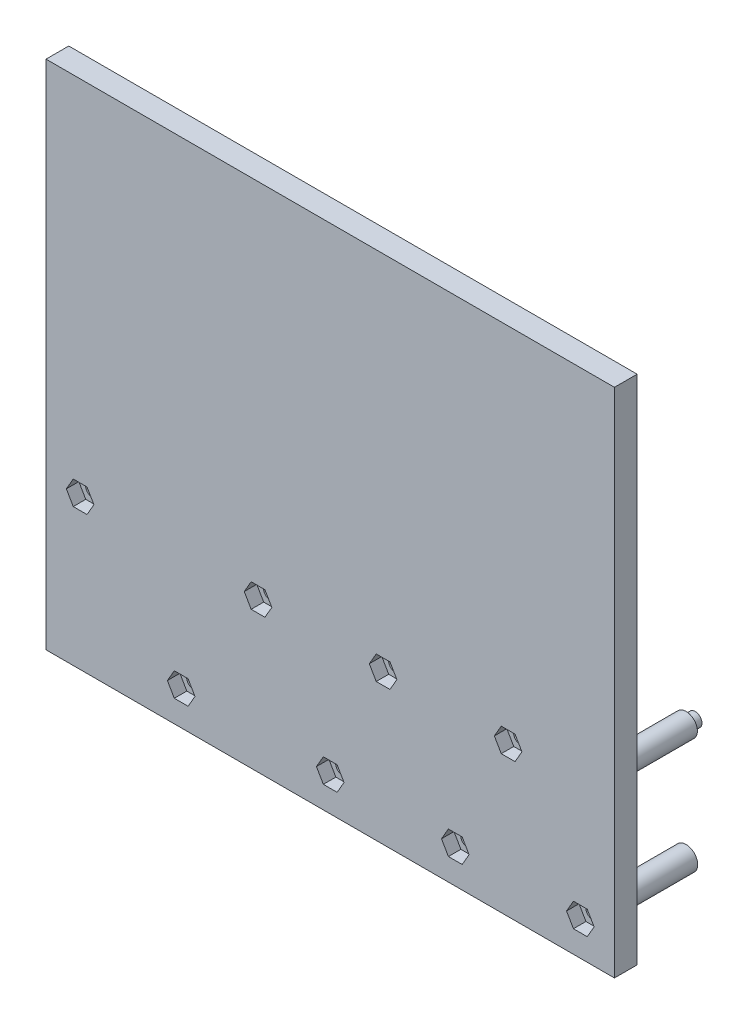
SolidWorks part; units mm, degrees
ref_plane "Front Plane" through (0, 0, 0) normal (0, 0, 1) x (1, 0, 0)
ref_plane "Top Plane" through (0, 0, 0) normal (0, 1, 0) x (1, 0, 0)
ref_plane "Right Plane" through (0, 0, 0) normal (1, 0, 0) x (0, 0, -1)
sketch "Sketch1" plane through (0, 0, 0) normal (0, 0, 1) x (1, 0, 0)
  line L1 (50, -45) -> (-50, -45)
  line L2 (50, -45) -> (50, 45)
  line L3 (50, 45) -> (-50, 45)
  line L4 (-50, -45) -> (-50, 45)
  line L5 (50, -45) -> (-50, 45) construction
  line L6 (50, 45) -> (-50, -45) construction
  point P0 (0, 0)
  dimension "D1" = 100
  dimension "D2" = 90
extrude "Boss-Extrude1" add sketch "Sketch1" along normal mid plane 4
sketch "Sketch2" plane through (0, 0, 2) normal (0, 0, 1) x (1, 0, 0)
  line L0 (50, -45) -> (50, 45) construction
  line L1 (-50, -45) -> (50, -45) construction
  circle A0 centre (44, -39) radius 1.25
  circle A1 centre (44, -18.68) radius 1.2
  circle A2 centre (31.3, -18.68) radius 1.25
  circle A3 centre (31.3, -39) radius 1.2
  circle A4 centre (31.3, -18.68) radius 2.05
  circle A5 centre (44, -18.68) radius 2
  circle A6 centre (31.3, -39) radius 2
  circle A7 centre (44, -39) radius 2.05
  dimension "D1" = 2.5
  dimension "D2" = 2.4
  dimension "D7" = 4
  dimension "D8" = 4.1
  dimension "D3" = 12.7
  dimension "D4" = 20.32
  dimension "D5" = 6
  dimension "D6" = 6
extrude "Boss-Extrude3" add sketch "Sketch2" against normal blind 18.6 contours A6 | A7 | A5 | A4
extrude "Cut-Extrude1" cut sketch "Sketch2<5>" against normal through all contours A2 | A0
sketch "Sketch2<5>" plane through (0, 0, 2) normal (0, 0, 1) x (1, 0, 0) same geometry as "Sketch2"
extrude "Boss-Extrude4" add sketch "Sketch2<6>" against normal blind 20.2 contours A3 | A1
sketch "Sketch2<6>" plane through (0, 0, 2) normal (0, 0, 1) x (1, 0, 0) same geometry as "Sketch2"
sketch "Sketch3" plane through (0, 0, 2) normal (0, 0, 1) x (1, 0, 0)
  line L0 (-50, -45) -> (50, -45) construction
  line L1 (30.0876, -16.58) -> (28.8751, -18.68)
  line L2 (28.8751, -18.68) -> (30.0876, -20.78)
  line L3 (30.0876, -20.78) -> (32.5124, -20.78)
  line L4 (32.5124, -20.78) -> (33.7249, -18.68)
  line L5 (33.7249, -18.68) -> (32.5124, -16.58)
  line L6 (32.5124, -16.58) -> (30.0876, -16.58)
  line L7 (42.7876, -36.9) -> (41.5751, -39)
  line L8 (41.5751, -39) -> (42.7876, -41.1)
  line L9 (42.7876, -41.1) -> (45.2124, -41.1)
  line L10 (45.2124, -41.1) -> (46.4249, -39)
  line L11 (46.4249, -39) -> (45.2124, -36.9)
  line L12 (45.2124, -36.9) -> (42.7876, -36.9)
  circle A0 centre (31.3, -18.68) radius 2.1 construction
  circle A1 centre (44, -39) radius 2.1 construction
  point P20 (0, 0)
  dimension "D1" = 4.2
  dimension "D2" = 4.2
extrude "Cut-Extrude2" cut sketch "Sketch3" against normal blind 2.2
pattern_linear "LPattern1" count 3 spacing 22 along (-1, 0, 0) of "Boss-Extrude3", "Cut-Extrude1", "Boss-Extrude4", "Cut-Extrude2"
sketch "Sketch4" plane through (0, 0, 2) normal (0, 0, 1) x (1, 0, 0)
  line L0 (-50, 45) -> (-50, -45) construction
  line L1 (-50, -45) -> (50, -45) construction
  circle A1 centre (-44, -39) radius 1.2
  circle A2 centre (-44, -39) radius 2
  circle A3 centre (-26.22, -39) radius 1.25
  circle A4 centre (-26.22, -39) radius 2.05
  circle A5 centre (-44, -18.68) radius 2.05
  circle A6 centre (-44, -18.68) radius 1.25
  circle A7 centre (-26.22, -18.68) radius 1.2
  circle A8 centre (-26.22, -18.68) radius 2
  point P12 (0, 0)
  point P13 (0, 0)
  point P14 (0, 0)
  point P15 (0, 0)
  dimension "D1" = 2.5
  dimension "D2" = 4.1
  dimension "D3" = 4
  dimension "D4" = 2.4
  dimension "D5" = 6
  dimension "D6" = 6
  dimension "D7" = 17.78
  dimension "D8" = 20.32
extrude "Boss-Extrude5" add sketch "Sketch4" against normal blind 18.6 contours A5 | A2 | A4 | A8
extrude "Cut-Extrude3" cut sketch "Sketch4<3>" against normal through all contours A3 | A6
sketch "Sketch4<3>" plane through (0, 0, 2) normal (0, 0, 1) x (1, 0, 0) same geometry as "Sketch4"
extrude "Boss-Extrude6" add sketch "Sketch4<4>" against normal blind 20.2 contours A1 | A7
sketch "Sketch4<4>" plane through (0, 0, 2) normal (0, 0, 1) x (1, 0, 0) same geometry as "Sketch4"
sketch "Sketch5" plane through (0, 0, 2) normal (0, 0, 1) x (1, 0, 0)
  line L0 (-50, -45) -> (50, -45) construction
  line L1 (-45.2124, -16.58) -> (-46.4249, -18.68)
  line L2 (-46.4249, -18.68) -> (-45.2124, -20.78)
  line L3 (-45.2124, -20.78) -> (-42.7876, -20.78)
  line L4 (-42.7876, -20.78) -> (-41.5751, -18.68)
  line L5 (-41.5751, -18.68) -> (-42.7876, -16.58)
  line L6 (-42.7876, -16.58) -> (-45.2124, -16.58)
  line L7 (-27.4324, -36.9) -> (-28.6449, -39)
  line L8 (-28.6449, -39) -> (-27.4324, -41.1)
  line L9 (-27.4324, -41.1) -> (-25.0076, -41.1)
  line L10 (-25.0076, -41.1) -> (-23.7951, -39)
  line L11 (-23.7951, -39) -> (-25.0076, -36.9)
  line L12 (-25.0076, -36.9) -> (-27.4324, -36.9)
  circle A0 centre (-44, -18.68) radius 2.1 construction
  circle A1 centre (-26.22, -39) radius 2.1 construction
  dimension "D1" = 4.2
  dimension "D2" = 4.2
extrude "Cut-Extrude4" cut sketch "Sketch5" against normal blind 2.2
